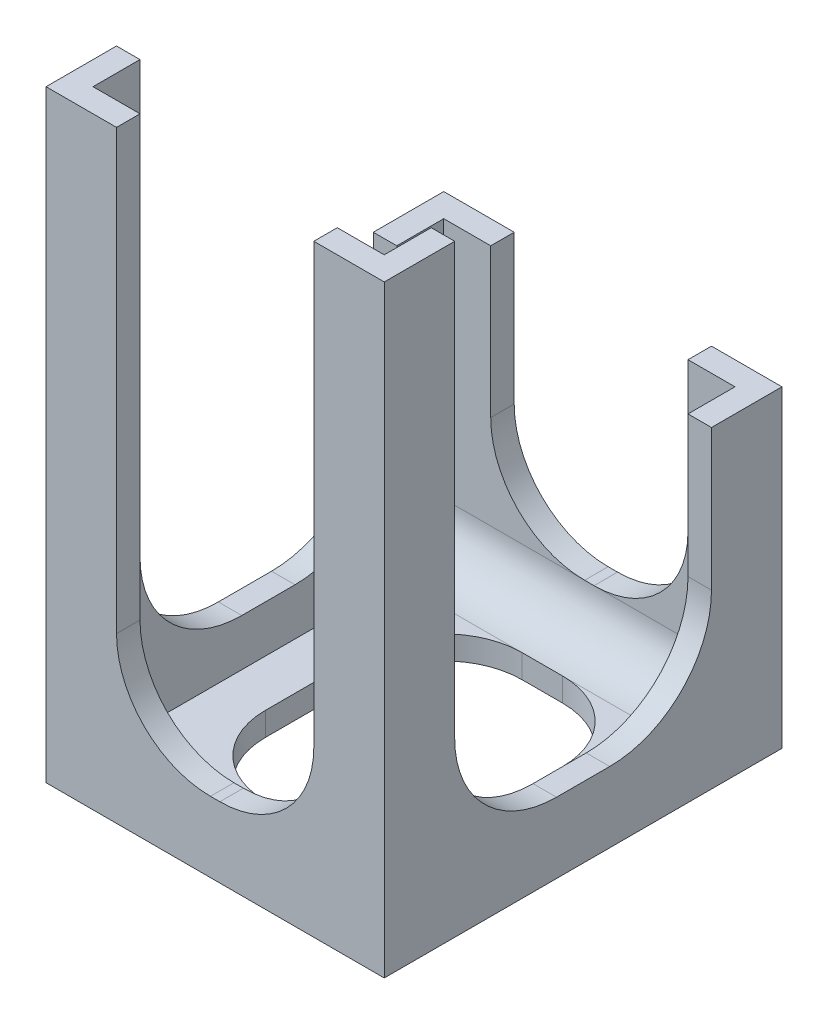
SolidWorks part; units mm, degrees
ref_plane "Front Plane" through (0, 0, 0) normal (0, 0, 1) x (1, 0, 0)
ref_plane "Top Plane" through (0, 0, 0) normal (0, 1, 0) x (1, 0, 0)
ref_plane "Right Plane" through (0, 0, 0) normal (1, 0, 0) x (0, 0, -1)
sketch "Sketch1" plane through (0, 0, 0) normal (0, 1, 0) x (1, 0, 0)
  line L1 (-76.5701, -45.4845) -> (-54.9701, -45.4845)
  line L2 (-76.5701, -45.4845) -> (-76.5701, -20.0845)
  line L3 (-76.5701, -20.0845) -> (-54.9701, -20.0845)
  line L4 (-54.9701, -45.4845) -> (-54.9701, -20.0845)
  dimension "D1" = 21.6
  dimension "D2" = 25.4
extrude "Boss-Extrude1" add sketch "Sketch1" along normal blind 38.5
sketch "Sketch2" plane through (0, 38.5, 0) normal (0, 1, 0) x (1, 0, 0)
  line L0 (-54.9701, -20.0845) -> (-76.5701, -20.0845) construction
  line L1 (-75.0701, -43.9845) -> (-56.4701, -43.9845)
  line L2 (-75.0701, -43.9845) -> (-75.0701, -21.5845)
  line L3 (-75.0701, -21.5845) -> (-56.4701, -21.5845)
  line L4 (-56.4701, -43.9845) -> (-56.4701, -21.5845)
  line L5 (-54.9701, -45.4845) -> (-54.9701, -20.0845) construction
  line L6 (-76.5701, -20.0845) -> (-76.5701, -45.4845) construction
  line L7 (-76.5701, -45.4845) -> (-54.9701, -45.4845) construction
  dimension "D1" = 1.5
  dimension "D2" = 1.5
  dimension "D3" = 1.5
  dimension "D4" = 1.5
extrude "Cut-Extrude1" cut sketch "Sketch2" against normal blind 37
sketch "Sketch3" plane through (-54.9701, 0, 0) normal (1, 0, 0) x (0, 0, -1)
  line L0 (-45.4845, 38.5) -> (-20.0845, 38.5) construction
  line L1 (-40.9845, 38.5) -> (-24.5845, 38.5)
  line L2 (-40.9845, 38.5) -> (-40.9845, 11)
  line L3 (-34.4845, 4.5) -> (-31.0845, 4.5)
  line L4 (-24.5845, 38.5) -> (-24.5845, 11)
  line L5 (-45.4845, 0) -> (-20.0845, 0) construction
  line L6 (-20.0845, 38.5) -> (-20.0845, 0) construction
  line L7 (-45.4845, 38.5) -> (-45.4845, 0) construction
  arc A0 (-31.0845, 4.5) -> (-24.5845, 11) centre (-31.0845, 11) ccw
  arc A1 (-40.9845, 11) -> (-34.4845, 4.5) centre (-34.4845, 11) ccw
  dimension "D4" = 6.5
  dimension "D1" = 4.5
  dimension "D2" = 4.5
  dimension "D3" = 4.5
sketch "Sketch5" plane through (0, 0, 45.4845) normal (0, 0, 1) x (1, 0, 0)
  line L0 (-76.5701, 38.5) -> (-54.9701, 38.5) construction
  line L1 (-72.0701, 38.5) -> (-59.4701, 38.5)
  line L2 (-72.0701, 38.5) -> (-72.0701, 10.5)
  line L3 (-66.0701, 4.5) -> (-65.4701, 4.5)
  line L4 (-59.4701, 38.5) -> (-59.4701, 10.5)
  line L5 (-76.5701, 38.5) -> (-76.5701, 0) construction
  line L6 (-54.9701, 38.5) -> (-54.9701, 0) construction
  line L7 (-76.5701, 0) -> (-54.9701, 0) construction
  arc A0 (-65.4701, 4.5) -> (-59.4701, 10.5) centre (-65.4701, 10.5) ccw
  arc A1 (-72.0701, 10.5) -> (-66.0701, 4.5) centre (-66.0701, 10.5) ccw
  dimension "D4" = 6
  dimension "D1" = 4.5
  dimension "D2" = 4.5
  dimension "D3" = 4.5
extrude "Cut-Extrude2" cut sketch "Sketch5" against normal blind 25.5
extrude "Cut-Extrude3" cut sketch "Sketch3" against normal blind 25.5
sketch "Sketch6" plane through (0, 1.5, 0) normal (0, 1, 0) x (1, 0, 0)
  line L0 (-75.0701, -21.5845) -> (-75.0701, -43.9845) construction
  line L1 (-67.0701, -40.9845) -> (-64.4701, -40.9845)
  line L2 (-72.0701, -35.9845) -> (-72.0701, -29.5845)
  line L3 (-67.0701, -24.5845) -> (-64.4701, -24.5845)
  line L4 (-59.4701, -35.9845) -> (-59.4701, -29.5845)
  line L5 (-56.4701, -21.5845) -> (-75.0701, -21.5845) construction
  line L6 (-56.4701, -43.9845) -> (-56.4701, -21.5845) construction
  line L7 (-75.0701, -43.9845) -> (-56.4701, -43.9845) construction
  arc A0 (-72.0701, -29.5845) -> (-67.0701, -24.5845) centre (-67.0701, -29.5845) cw
  arc A1 (-64.4701, -24.5845) -> (-59.4701, -29.5845) centre (-64.4701, -29.5845) cw
  arc A2 (-64.4701, -40.9845) -> (-59.4701, -35.9845) centre (-64.4701, -35.9845) ccw
  arc A3 (-67.0701, -40.9845) -> (-72.0701, -35.9845) centre (-67.0701, -35.9845) cw
  point P4 (-57.8751, -25.0362)
  dimension "D5" = 5
  dimension "D1" = 3
  dimension "D2" = 3
  dimension "D3" = 3
  dimension "D4" = 3
extrude "Cut-Extrude4" cut sketch "Sketch6" against normal blind 1.5
fillet "Fillet2" radius 3 1 edges at (-65.7701, 1.5, 43.9845) type face fillet first side face at (-65.7701, 1.5, 32.7845) second side face at (-65.7701, 18.4515, 43.9845)
fillet "Fillet3" radius 3 1 edges at (-65.7701, 1.5, 21.5845) type face fillet first side face at (-65.7701, 1.5, 32.2845) second side face at (-65.7701, 18.4515, 21.5845)
sketch "Sketch7" plane through (0, 38.5, 0) normal (0, 1, 0) x (1, 0, 0)
  line L1 (-54.9701, -24.5845) -> (-76.5701, -24.5845)
  line L2 (-54.9701, -24.5845) -> (-54.9701, -20.0845)
  line L3 (-54.9701, -20.0845) -> (-76.5701, -20.0845)
  line L4 (-76.5701, -24.5845) -> (-76.5701, -20.0845)
  point P4 (-76.2047, -19.3918)
extrude "Cut-Extrude5" cut sketch "Sketch7" against normal blind 18.5 contours L2 L1 L4 L3
